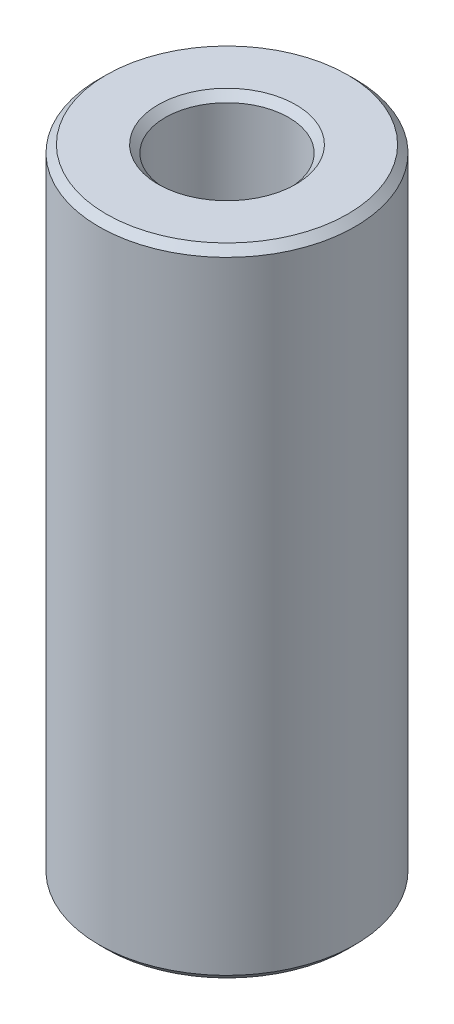
SolidWorks part; units mm, degrees
ref_plane "Front Plane" through (0, 0, 0) normal (0, 0, 1) x (1, 0, 0)
ref_plane "Top Plane" through (0, 0, 0) normal (0, 1, 0) x (1, 0, 0)
ref_plane "Right Plane" through (0, 0, 0) normal (1, 0, 0) x (0, 0, -1)
sketch "Sketch1" plane through (0, 0, 0) normal (0, 1, 0) x (1, 0, 0)
  circle A0 centre (0, 0) radius 42.5
  dimension "SLEEVE_OD" = 85
extrude "Boss-Extrude1" add sketch "Sketch1" along normal blind 211.2996
sketch "Sketch2" plane through (0, 0, 0) normal (0, 1, 0) x (1, 0, 0)
  circle A0 centre (0, 0) radius 20.4692
  dimension "BORE_D" = 40.9384
extrude "Cut-Extrude1" cut sketch "Sketch2" along normal through all
chamfer "Chamfer1" distance 2.4091 angle 45.449 4 edges at (0, 211.2996, 20.4692) (0, 0, 20.4692) (0, 0, 42.5) (0, 211.2996, 42.5) first distance on face at (0, 211.2996, 20.4692) first distance on face at (0, 0, 20.4692) first distance on face at (0, 211.2996, 42.5)
